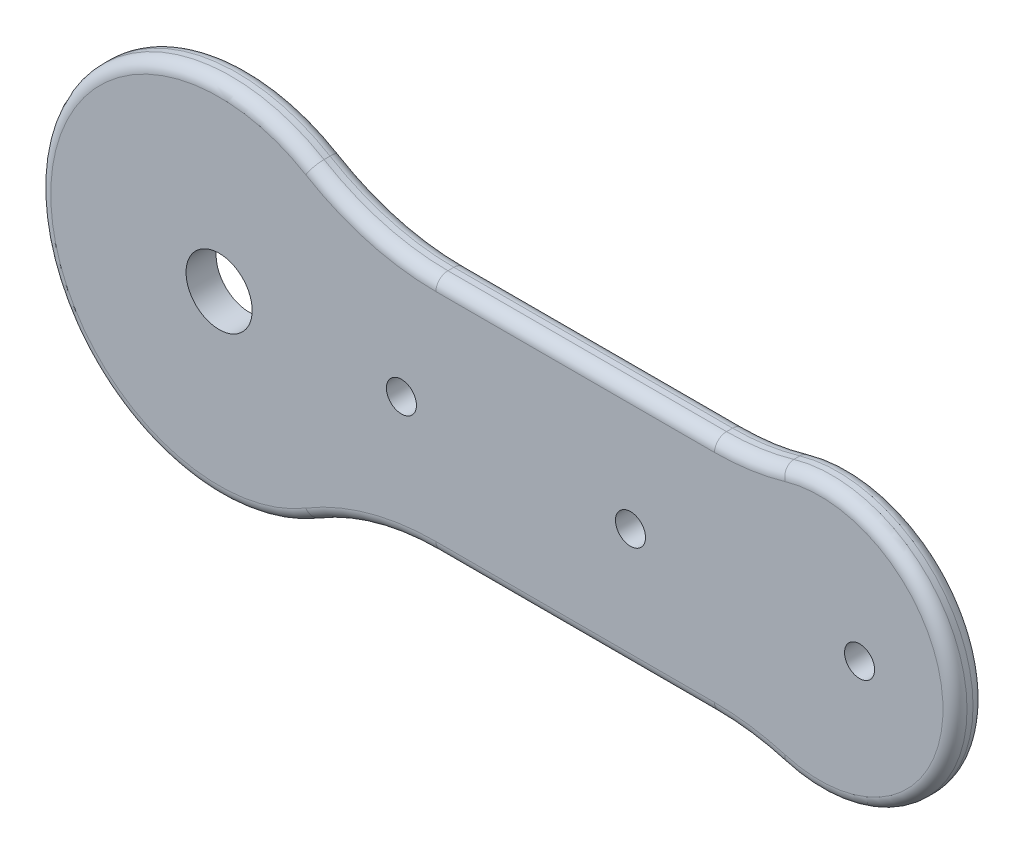
SolidWorks part; units mm, degrees
material "Copper"
ref_plane "Front Plane" through (0, 0, 0) normal (0, 0, 1) x (1, 0, 0)
ref_plane "Top Plane" through (0, 0, 0) normal (0, 1, 0) x (1, 0, 0)
ref_plane "Right Plane" through (0, 0, 0) normal (1, 0, 0) x (0, 0, -1)
sketch "Sketch1" plane through (0, 0, 0) normal (0, 0, 1) x (1, 0, 0)
  line L1 (-99.9, 40) -> (99.9, 40)
  line L2 (-99.9, 40) -> (-99.9, -40)
  line L3 (-99.9, -40) -> (99.9, -40)
  line L4 (99.9, 40) -> (99.9, -40)
  line L5 (-99.9, 40) -> (99.9, -40) construction
  line L6 (-99.9, -40) -> (99.9, 40) construction
  circle A0 centre (99.9, 0) radius 45
  circle A1 centre (-99.9, 0) radius 60
  circle A2 centre (-99.9, 0) radius 11
  circle A4 centre (36.95, 0) radius 5
  circle A5 centre (-39.25, 0) radius 5
  circle A7 centre (113.15, 0) radius 5
  point P0 (0, 0)
  point P18 (-159.9, 0)
  point P19 (144.9, 0)
  dimension "D2" = 120
  dimension "D3" = 90
  dimension "D5" = 22
  dimension "D6" = 10
  dimension "D7" = 10
  dimension "D8" = 10
  dimension "D10" = 31.75
  dimension "D11" = 76.2
  dimension "D12" = 76.2
  dimension "D1" = 80
  dimension "D4" = 304.8
extrude "Boss-Extrude1" add sketch "Sketch1" along normal blind 10 contours A2 L2 L1 A1 L3 | A1 L1 L2 A2 L3 | A1 L3 A0 A4 L1 A5 | A4 A0 L3 L4 L1 | L4 L3 A0 L1 region at (-118.0657, 0, 0) region at (-71.3065, 0, 0) region at (8.7018, 0, 0) region at (122.7435, 37.4723, 0) region at (80.2846, 0, 0)
fillet "Fillet1" radius 80 4 edges at (-55.1786, -40, 5) (-55.1786, 40, 5) (79.2845, -40, 5) (79.2845, 40, 5)
fillet "Fillet2" radius 4 16 edges at (18.5555, 40, 0) (-159.9, 0, 0) (18.5555, -40, 0) (144.9, 0, 0) (144.9, 0, 10) (18.5555, -40, 10) (-159.9, 0, 10) (18.5555, 40, 10) (-49.1699, -42.9101, 0) (-49.1699, -42.9101, 10) (-49.1699, 42.9101, 0) (-49.1699, 42.9101, 10) (76.2137, -40.804, 0) (76.2137, -40.804, 10) (76.2137, 40.804, 0) (76.2137, 40.804, 10)
